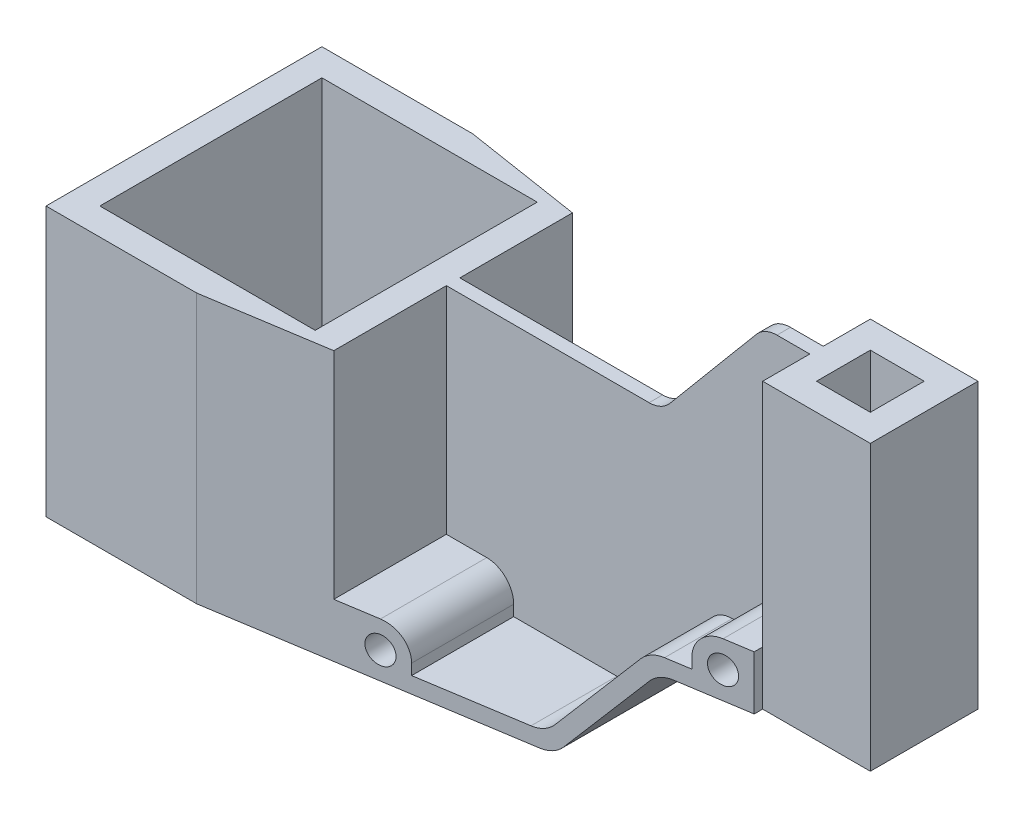
SolidWorks part; units mm, degrees
material "1060 Alloy"
ref_plane "Front Plane" through (0, 0, 0) normal (0, 0, 1) x (1, 0, 0)
ref_plane "Top Plane" through (0, 0, 0) normal (0, 1, 0) x (1, 0, 0)
ref_plane "Right Plane" through (0, 0, 0) normal (1, 0, 0) x (0, 0, -1)
sketch "Sketch1" plane through (0, 0, 0) normal (0, 1, 0) x (1, 0, 0)
  line L1 (0, 0) -> (-275, 0)
  line L2 (0, 0) -> (0, -102.5)
  line L3 (0, -102.5) -> (-275, -102.5)
  line L4 (-275, 0) -> (-275, -102.5)
  dimension "D1" = 275
  dimension "D2" = 102.5
extrude "Boss-Extrude1" add sketch "Sketch1" along normal blind 145.5
sketch "Sketch2" plane through (0, 145.5, 0) normal (0, 1, 0) x (1, 0, 0)
  line L0 (-275, -102.5) -> (0, -102.5) construction
  line L1 (-275, 0) -> (-107, 0)
  line L2 (-275, 0) -> (-275, -102.5)
  line L3 (-275, -102.5) -> (-107, -102.5)
  line L4 (-107, 0) -> (-107, -102.5)
  dimension "D1" = 168
extrude "Cut-Extrude1" cut sketch "Sketch2" against normal blind 45.5
sketch "Sketch3" plane through (0, 100, 0) normal (0, 1, 0) x (1, 0, 0)
  line L0 (-275, -51.25) -> (-96.5463, -51.25) construction
  line L1 (-275, 0) -> (-275, -102.5) construction
  line L2 (-107, 0) -> (-175, 0)
  line L3 (-107, -102.5) -> (-175, -102.5)
  line L4 (-107, -102.5) -> (-107, -53.75)
  line L5 (-107, -53.75) -> (-175, -53.75)
  line L6 (-175, -102.5) -> (-175, -53.75)
  line L7 (-107, 0) -> (-107, -48.75)
  line L8 (-175, 0) -> (-175, -48.75)
  line L9 (-107, -48.75) -> (-175, -48.75)
  dimension "D1" = 2.5
  dimension "D2" = 100
extrude "Cut-Extrude2" cut sketch "Sketch3" against normal blind 80
sketch "Sketch4" plane through (0, 100, 0) normal (0, 1, 0) x (1, 0, 0)
  line L0 (-275, 0) -> (-275, -102.5) construction
  line L1 (-265, -10) -> (-185, -10)
  line L2 (-265, -10) -> (-265, -92.5)
  line L3 (-265, -92.5) -> (-185, -92.5)
  line L4 (-185, -10) -> (-185, -92.5)
  line L5 (-175, 0) -> (-175, -48.75) construction
  line L6 (-175, 0) -> (-275, 0) construction
  line L7 (-275, -102.5) -> (-175, -102.5) construction
  dimension "D1" = 10
  dimension "D2" = 10
  dimension "D3" = 10
  dimension "D4" = 10
extrude "Cut-Extrude3" cut sketch "Sketch4" against normal through all
sketch "Sketch5" plane through (0, 0, 102.5) normal (0, 0, 1) x (1, 0, 0)
  line L0 (-107, 6) -> (-150, 6)
  line L1 (-275, 100) -> (-275, 0) construction
  line L2 (-275, 0) -> (0, 0) construction
  line L3 (-160, 20) -> (-175, 20)
  line L4 (-107, 20) -> (-175, 20) construction
  line L5 (-150, 10) -> (-150, 6)
  line L6 (-175, 20) -> (-175, 100)
  line L7 (-175, 100) -> (-107, 100)
  line L8 (-107, 100) -> (-107, 6)
  circle A0 centre (-160, 10) radius 5
  arc A1 (-160, 20) -> (-150, 10) centre (-160, 10) cw
  dimension "D4" = 10
  dimension "D1" = 168
  dimension "D2" = 6
  dimension "D3" = 115
extrude "Cut-Extrude4" cut sketch "Sketch5" against normal blind 48.75
sketch "Sketch6" plane through (0, 0, 0) normal (0, 0, -1) x (-1, 0, 0)
  line L0 (107, 100) -> (175, 100)
  line L1 (175, 100) -> (175, 20)
  line L2 (175, 20) -> (160, 20)
  line L3 (150, 10) -> (150, 6)
  line L4 (150, 6) -> (107, 6)
  line L5 (107, 6) -> (107, 100)
  arc A0 (160, 20) -> (150, 10) centre (160, 10) ccw
  circle A1 centre (160, 10) radius 5
extrude "Cut-Extrude5" cut sketch "Sketch6" against normal blind 48.75
extrude "Cut-Extrude6" cut sketch "Sketch5<2>" against normal through all contours A0
sketch "Sketch5<2>" plane through (0, 0, 102.5) normal (0, 0, 1) x (1, 0, 0) same geometry as "Sketch5"
sketch "Sketch7" plane through (0, 0, 102.5) normal (0, 0, 1) x (1, 0, 0)
  line L0 (-107, 6) -> (-60.6598, 61.226)
  line L1 (-150, 6) -> (-107, 6) construction
  line L2 (-70.6382, 40) -> (-104.2022, 0)
  line L3 (-275, 0) -> (0, 0) construction
  line L4 (-70.6382, 40) -> (0, 40)
  line L5 (0, 145.5) -> (0, 0) construction
  line L6 (0, 40) -> (0, 0)
  line L7 (0, 0) -> (-104.2022, 0)
  line M13 (-275, 0) -> (0, 0)
  line M14 (0, 0) -> (0, 145.5)
  dimension "D1" = 130
  dimension "D2" = 6
  dimension "D3" = 40
extrude "Cut-Extrude7" cut sketch "Sketch7" against normal through all contours L4 L2 M13 M14 region at (-44.247, 18.7202, 102.5)
sketch "Sketch8" plane through (0, 0, 102.5) normal (0, 0, 1) x (1, 0, 0)
  line L0 (-73.436, 46) -> (-60, 46)
  line L1 (-107, 100) -> (-95.0268, 100)
  line L2 (-95.0268, 100) -> (-56.8477, 145.5)
  line L3 (-107, 6) -> (-60.6598, 61.226) construction
  line L4 (0, 145.5) -> (0, 40) construction
  line L5 (-70.6382, 40) -> (0, 40) construction
  line L6 (-50, 60) -> (0, 60)
  line L7 (-40, 145.5) -> (-40, 60)
  line L8 (-107, 145.5) -> (0, 145.5) construction
  line L9 (-60, 50) -> (-60, 46)
  line L10 (-56.8477, 145.5) -> (-95.0268, 100)
  line L11 (-107, 145.5) -> (-107, 100)
  line L12 (-70.6382, 40) -> (-104.2022, 0) construction
  circle A0 centre (-50, 50) radius 5
  arc A1 (-50, 60) -> (-60, 50) centre (-50, 50) ccw
  line M11 (0, 145.5) -> (-107, 145.5)
  line M12 (-107, 145.5) -> (-107, 6)
  dimension "D5" = 10
  dimension "D1" = 6
  dimension "D2" = 20
  dimension "D3" = 50
  dimension "D4" = 40
  dimension "D6" = 10
  dimension "D7" = 51.25
extrude "Cut-Extrude8" cut sketch "Sketch8" against normal through all contours L1 L2 M11 M12 region at (-89.5134, 127.4103, 102.5)
sketch "Sketch9" plane through (0, 0, 102.5) normal (0, 0, 1) x (1, 0, 0)
  line L0 (-40, 145.5) -> (-40, 60)
  line L1 (-40, 60) -> (-50, 60)
  line L2 (-60, 50) -> (-60, 46)
  line L3 (-60, 46) -> (-73.436, 46)
  line L4 (-73.436, 46) -> (-107, 6)
  line L5 (-107, 6) -> (-107, 100)
  line L6 (-107, 100) -> (-95.0268, 100)
  line L7 (-95.0268, 100) -> (-56.8477, 145.5)
  line L8 (-56.8477, 145.5) -> (-40, 145.5)
  arc A0 (-50, 60) -> (-60, 50) centre (-50, 50) ccw
extrude "Cut-Extrude9" cut sketch "Sketch9" against normal blind 48.75
sketch "Sketch10" plane through (0, 0, 0) normal (0, 0, -1) x (-1, 0, 0)
  line L0 (40, 145.5) -> (40, 60)
  line L1 (40, 60) -> (50, 60)
  line L2 (60, 50) -> (60, 46)
  line L3 (60, 46) -> (73.436, 46)
  line L4 (73.436, 46) -> (107, 6)
  line L5 (107, 6) -> (107, 100)
  line L6 (107, 100) -> (95.0268, 100)
  line L7 (95.0268, 100) -> (56.8477, 145.5)
  line L8 (56.8477, 145.5) -> (40, 145.5)
  arc A0 (50, 60) -> (60, 50) centre (50, 50) cw
  circle A1 centre (50, 50) radius 5
extrude "Cut-Extrude10" cut sketch "Sketch10" against normal blind 48.75
sketch "Sketch11" plane through (0, 145.5, 0) normal (0, 1, 0) x (1, 0, 0)
  line L0 (-40, -71.25) -> (0, -71.25)
  line L4 (-40, -53.75) -> (-40, -102.5) construction
  line L5 (0, -102.5) -> (0, 0) construction
  line L6 (-40, -102.5) -> (0, -102.5) construction
  line L8 (-40, -48.75) -> (-40, 0) construction
  line L9 (-40, -31.25) -> (0, -31.25)
  line L11 (-40, -31.25) -> (-40, 0)
  line L12 (-40, 0) -> (0, 0)
  line L13 (0, 0) -> (0, -31.25)
  line L14 (0, -71.25) -> (0, -102.5)
  line L15 (0, -102.5) -> (-40, -102.5)
  line L16 (-40, -102.5) -> (-40, -71.25)
  dimension "D1" = 31.25
  dimension "D2" = 40
extrude "Cut-Extrude11" cut sketch "Sketch11" against normal through all
sketch "Sketch12" plane through (0, 145.5, 0) normal (0, 1, 0) x (1, 0, 0)
  line L0 (-40, -31.25) -> (0, -31.25) construction
  line L1 (-30, -41.25) -> (-10, -41.25)
  line L2 (-30, -41.25) -> (-30, -61.25)
  line L3 (-30, -61.25) -> (-10, -61.25)
  line L4 (-10, -41.25) -> (-10, -61.25)
  line L5 (0, -71.25) -> (-40, -71.25) construction
  line L6 (-40, -48.75) -> (-40, -31.25) construction
  line L7 (0, -71.25) -> (0, -31.25) construction
  dimension "D1" = 10
  dimension "D2" = 10
  dimension "D3" = 10
  dimension "D4" = 10
extrude "Cut-Extrude12" cut sketch "Sketch12" against normal through all
sketch "Sketch13" plane through (0, 0, 48.75) normal (0, 0, -1) x (-1, 0, 0)
  circle A0 centre (50, 50) radius 5 construction
  circle A1 centre (50, 50) radius 5
extrude "Cut-Extrude13" cut sketch "Sketch13" against normal through all
sketch "Sketch14" plane through (0, 100, 0) normal (0, 1, 0) x (1, 0, 0)
  line L0 (-225, 0) -> (-225, -118.0435) construction
  line L1 (-175, 0) -> (-275, 0) construction
  line L2 (-219, 0) -> (-219, -102.5) construction
  line L3 (-275, -102.5) -> (-175, -102.5) construction
  line L4 (-20, -31.25) -> (-20, -71.25) construction
  line L5 (-40, -31.25) -> (0, -31.25) construction
  line L6 (0, -71.25) -> (-40, -71.25) construction
  line L7 (-219, 0) -> (-20, -31.25)
  line L8 (-20, -31.25) -> (-20, 0)
  line L9 (-20, 0) -> (-219, 0)
  line L10 (-219, -102.5) -> (-20, -71.25)
  line L11 (-20, -71.25) -> (-20, -102.5)
  line L12 (-20, -102.5) -> (-219, -102.5)
  dimension "D1" = 6
extrude "Cut-Extrude14" cut sketch "Sketch14" against normal through all
fillet "Fillet1" radius 10 6 edges at (-56.8477, 145.5, 51.25) (-95.0268, 100, 51.25) (-107, 6, 33.169) (-73.436, 46, 35.8043) (-107, 6, 69.331) (-73.436, 46, 66.6957)
fillet "Fillet2" radius 10 2 edges at (-70.6382, 40, 51.25) (-104.2022, 0, 51.25)
